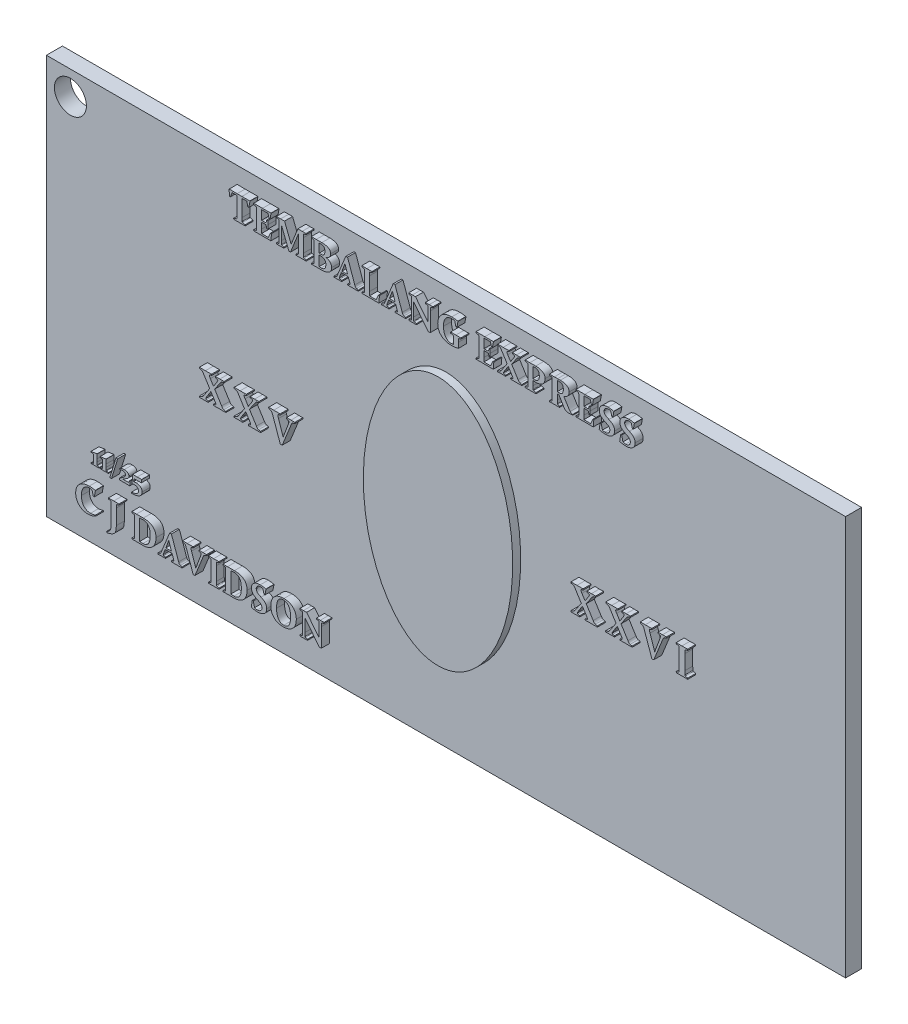
SolidWorks part; units mm, degrees
ref_plane "Front Plane" through (0, 0, 0) normal (0, 0, 1) x (1, 0, 0)
ref_plane "Top Plane" through (0, 0, 0) normal (0, 1, 0) x (1, 0, 0)
ref_plane "Right Plane" through (0, 0, 0) normal (1, 0, 0) x (0, 0, -1)
sketch "Sketch1" plane through (0, 0, 0) normal (0, 0, 1) x (1, 0, 0)
  line L1 (-50, 25) -> (50, 25)
  line L2 (-50, 25) -> (-50, -25)
  line L3 (-50, -25) -> (50, -25)
  line L4 (50, 25) -> (50, -25)
  line L5 (-50, 25) -> (50, -25) construction
  line L6 (-50, -25) -> (50, 25) construction
  point P0 (0, 0)
  dimension "D1" = 100
  dimension "D2" = 50
extrude "Boss-Extrude1" add sketch "Sketch1" along normal blind 2
sketch "Sketch2" plane through (0, 0, 0) normal (0, 0, 1) x (1, 0, 0)
  line L0 (-50, 0) -> (50, 0) construction
  line L1 (50, -25) -> (50, 25) construction
  line L2 (0, 25) -> (0, -25) construction
  line L3 (-50, -25) -> (50, -25) construction
  ellipse E0 centre (0, 0) end of major axis (0, 15.6635) minor radius 9.3477
  text T1 "TEMBALANG EXPRESS" font "Constantia" height in points 11
  text T2 "C J DAVIDSON" font "Constantia" height in points 11
  text T4 "X X V" font "Constantia" height in points 12
  text T5 "11/25" font "Constantia" height in points 8
  text T6 "X X V I" font "Constantia" height in points 12
  point P16 (0, 0)
  point P21 (0, 0)
extrude "Boss-Extrude4" add sketch "Sketch2" along normal blind 3
sketch "Sketch5" plane through (0, 0, 0) normal (0, 0, 1) x (1, 0, 0)
  line L0 (-50, 25) -> (-50, -25) construction
  line L1 (50, 25) -> (-50, 25) construction
  circle A0 centre (-47, 22) radius 2
  point P4 (0, 0)
  point P6 (-46.5855, 23.8591)
  dimension "D1" = 3
  dimension "D3" = 4
  dimension "D2" = 3
extrude "Cut-Extrude1" cut sketch "Sketch5" along normal blind 3
